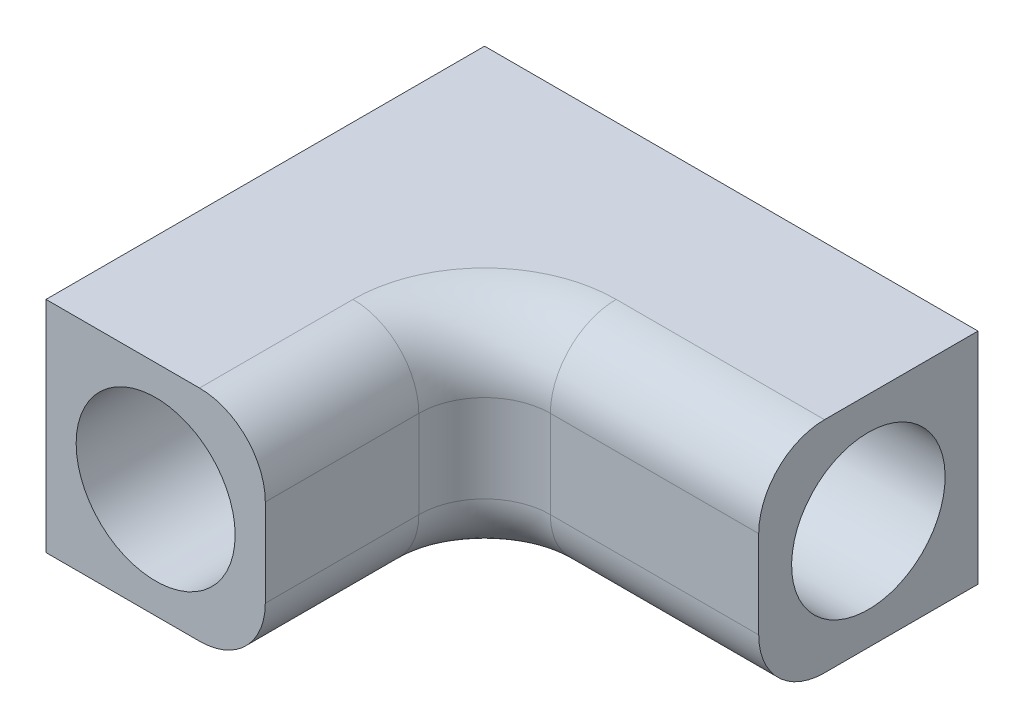
SolidWorks part; units mm, degrees
ref_plane "Спереди" through (0, 0, 0) normal (0, 0, 1) x (1, 0, 0)
ref_plane "Сверху" through (0, 0, 0) normal (0, 1, 0) x (1, 0, 0)
ref_plane "Справа" through (0, 0, 0) normal (1, 0, 0) x (0, 0, -1)
sketch "Эскиз2" plane through (0, 0, 0) normal (0, 0, 1) x (1, 0, 0)
  line L7 (-10, 10) -> (10, 10)
  line L8 (-10, 10) -> (-10, -10)
  line L9 (-10, -10) -> (10, -10)
  line L10 (10, 10) -> (10, -10)
  line L11 (-10, 10) -> (10, -10) construction
  line L12 (-10, -10) -> (10, 10) construction
  point P0 (0, 0)
  dimension "D2" = 20
extrude "Основа под дуло" add sketch "Эскиз2" along normal blind 40
sketch "Эскиз4" plane through (10, 0, 0) normal (1, 0, 0) x (0, 0, -1)
  line L0 (-40, 10) -> (0, 10) construction
  line L1 (-20, 10) -> (0, 10)
  line L2 (-20, 10) -> (-20, -10)
  line L3 (-20, -10) -> (0, -10)
  line L4 (0, 10) -> (0, -10)
  line L5 (-20, 10) -> (0, -10) construction
  line L6 (-20, -10) -> (0, 10) construction
  point P0 (-10, 0)
extrude "Основа под подачу снарядов" add sketch "Эскиз4" along normal blind 25
sketch "Эскиз7" plane through (35, 0, 0) normal (1, 0, 0) x (0, 0, -1)
  circle A0 centre (-10, 0) radius 6
  point P0 (-10, 0)
  dimension "D3" = 12
  dimension "D2" = 10
extrude "Дуло" cut sketch "Эскиз7" against normal offset from surface (44 mm away) 1 up to face at (-10, 0, 20)
sketch "Эскиз8" plane through (0, 0, 40) normal (0, 0, 1) x (1, 0, 0)
  circle A0 centre (0, 0) radius 6
  dimension "D1" = 12
extrude "Под подачу снарядов" cut sketch "Эскиз8" against normal up to next
sketch "Эскиз9" plane through (0, 0, 40) normal (0, 0, 1) x (1, 0, 0)
  circle A0 centre (0, 0) radius 7.25
  dimension "D1" = 14.5
extrude "Углубление под трубку для подачи снапрядов" cut sketch "Эскиз9" against normal blind 20
sketch "Эскиз10" plane through (35, 0, 0) normal (1, 0, 0) x (0, 0, -1)
  circle A0 centre (-10, 0) radius 7
  dimension "D1" = 14
extrude "Углубление под трубку-дуло" cut sketch "Эскиз10" against normal blind 20
sketch "Эскиз11" plane through (-10, 0, 0) normal (-1, 0, 0) x (0, 0, 1)
  circle A0 centre (10, 0) radius 4
  dimension "D1" = 8
extrude "Углубление под снаряд" cut sketch "Эскиз11" against normal up to next
sketch "Эскиз14" plane through (0, 0, 0) normal (0, 0, -1) x (-1, 0, 0)
  line L0 (-35, 10) -> (-35, 14)
  line L1 (-35, 14) -> (-32.5, 14)
  line L2 (-32.5, 14) -> (-32.5, 19)
  line L3 (-32.5, 19) -> (-35, 19)
  line L4 (-35, 19) -> (-35, 23)
  line L5 (-35, 23) -> (-25, 23)
  line L6 (-25, 23) -> (-25, 14)
  line L7 (-35, 10) -> (10, 10) construction
  line L8 (-21, 10) -> (-35, 10)
  line L9 (-25, 14) -> (-21, 10)
  dimension "D1" = 2.5
  dimension "D2" = 5
  dimension "D3" = 10
  dimension "D4" = 4
  dimension "D5" = 45
extrude "Выступ под резинки" [suppressed] add sketch "Эскиз14" against normal blind 9 from offset 5 offset against normal yes
chamfer "Фаска1" [suppressed] distance 2 angle 45
fillet "Скругление2" radius 6 5 edges at (10, 0, 20) (10, 10, 30) (10, -10, 30) (22.5, -10, 20) (22.5, 10, 20)
fillet "Скругление5" radius 1 1 edges at (-9, 4, 10)
fillet "Скругление6" [suppressed] radius 5
split "Разделить1" [suppressed] bodies to split 113
